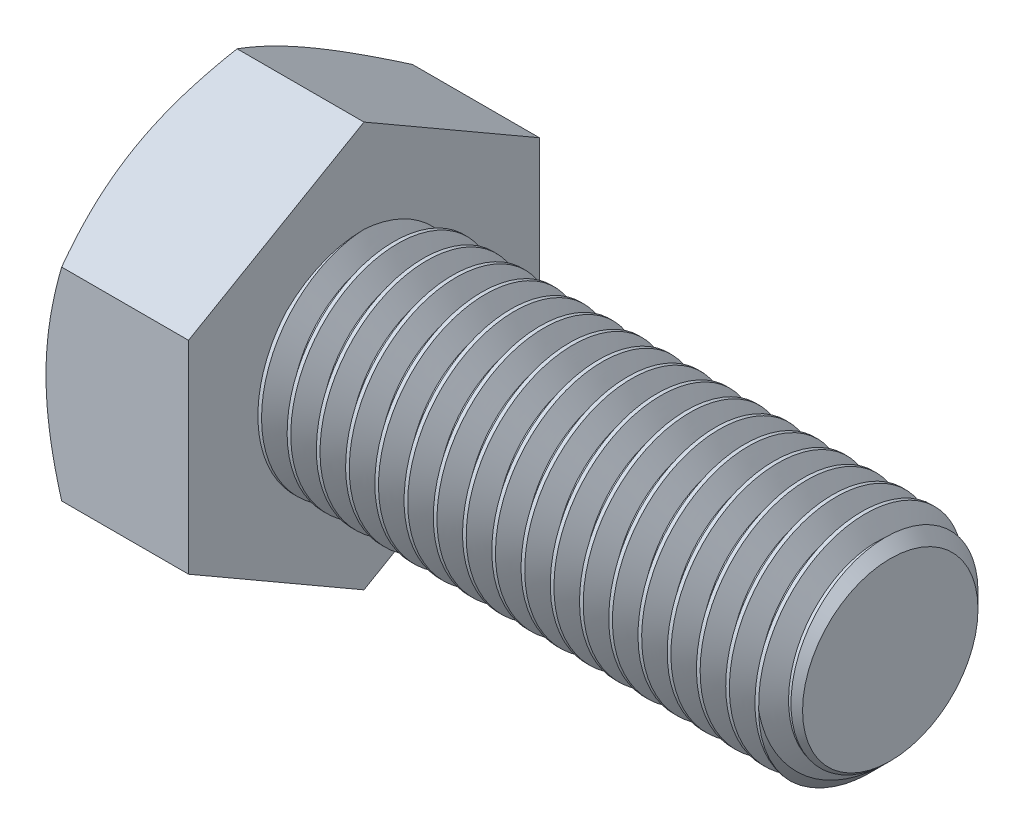
SolidWorks part; units mm, degrees
ref_plane "Front Plane" through (0, 0, 0) normal (0, 0, 1) x (1, 0, 0)
ref_plane "Top Plane" through (0, 0, 0) normal (0, 1, 0) x (1, 0, 0)
ref_plane "Right Plane" through (0, 0, 0) normal (1, 0, 0) x (0, 0, -1)
sketch "Sketch1" plane through (0, 0, 0) normal (0, 0, 1) x (1, 0, 0)
  line L0 (-12.1047, 0) -> (12.1047, 0) construction
  line L1 (12.1047, 3.9688) -> (12.1047, -3.9688) construction
  line L2 (-6.9453, 6.35) -> (-6.9453, -6.35) construction
  line L3 (-12.1047, 6.35) -> (-12.1047, -6.35) construction
  point P9 (-6.9453, 0)
  point P10 (8.4005, -3.9688)
  dimension "Screw Dia" = 7.9375
  dimension "Hex" = 12.7
  dimension "Head Ht" = 5.1594
  dimension "Screw Lenght" = 19.05
  dimension "D1" = 3.7042
ref_plane "Plane2" through (12.1047, 0, 0) normal (1, 0, 0) x (0, 0, -1)
sketch "Sketch5" plane through (12.1047, 0, 0) normal (1, 0, 0) x (0, 0, -1)
  circle A0 centre (0, 0) radius 3.9688
extrude "Boss-Extrude3" add sketch "Sketch5" against normal up to vertex (19.05 mm away) up to point (-6.9453, 0, 0)
sketch "Sketch9" plane through (12.1047, 0, 0) normal (1, 0, 0) x (0, 0, -1)
  circle A1 centre (0, 0) radius 3.9688
  circle A2 centre (0, 0) radius 3.9688
  dimension "D1" = 0
curve "Helix/Spiral1" pitch 1.0583 height 20.1083 turns 19 parameters "Pitch"=1.0583
chamfer "Chamfer1" distance 0.7937 angle 45 1 edges at (12.1047, 0, -3.9688)
sketch "Sketch10" plane through (0, 0, 0) normal (0, 0, 1) x (1, 0, 0)
  line L0 (12.1047, 3.9688) -> (12.5016, 3.2813)
  line L1 (12.5016, 3.2813) -> (12.6339, 3.2813)
  line L2 (12.6339, 3.2813) -> (13.0307, 3.9688)
  line L3 (12.1047, 3.9688) -> (13.0307, 3.9688)
  line L4 (12.5677, 3.9688) -> (12.5677, 3.2813) construction
  line L5 (12.3031, 3.625) -> (12.8323, 3.625) construction
  dimension "D1" = 60
  dimension "D2" = 0.1323
  dimension "D3" = 0.5292
sweep "Cut-Sweep1" cut profiles "Sketch10" path "Helix/Spiral1" align with end faces yes
sketch "Sketch6" plane through (-6.9453, 0, 0) normal (-1, 0, 0) x (0, 0, 1)
  line L0 (0, 6.35) -> (0, -6.35) construction
  line L1 (6.35, 3.6662) -> (0, 7.3323)
  line L2 (0, 7.3323) -> (-6.35, 3.6662)
  line L3 (-6.35, 3.6662) -> (-6.35, -3.6662)
  line L4 (-6.35, -3.6662) -> (0, -7.3323)
  line L5 (0, -7.3323) -> (6.35, -3.6662)
  line L6 (6.35, -3.6662) -> (6.35, 3.6662)
  circle A0 centre (0, 0) radius 6.35 construction
extrude "Boss-Extrude4" add sketch "Sketch6" along normal up to vertex (5.1594 mm away) up to point (-12.1047, -6.35, 0)
sketch "Sketch7" plane through (-12.1047, 0, 0) normal (-1, 0, 0) x (0, 0, 1)
  circle A0 centre (0, 0) radius 6.35 construction
  circle A1 centre (0, 0) radius 6.35
sketch "Sketch8" plane through (-12.1047, 0, 0) normal (-1, 0, 0) x (0, 0, 1)
  circle A0 centre (0, 0) radius 6.35 construction
  circle A1 centre (0, 0) radius 6.35
extrude "Cut-Extrude3" cut sketch "Sketch8" against normal through all draft 60 flip side to cut
equation "\"D2@Sketch10\" = \"Pitch@Helix/Spiral1\"*.125"
equation "\"D3@Sketch10\" = \"Pitch@Helix/Spiral1\"*.5"
equation "\"D3@Helix/Spiral1\" = \"Screw Lenght@Sketch1\"+\"Pitch@Helix/Spiral1\""
equation "\"D1@Chamfer1\" = \"Pitch@Helix/Spiral1\"*.75"
equation "\"D1@Sketch1\" = \"Pitch@Helix/Spiral1\"*3.5"
